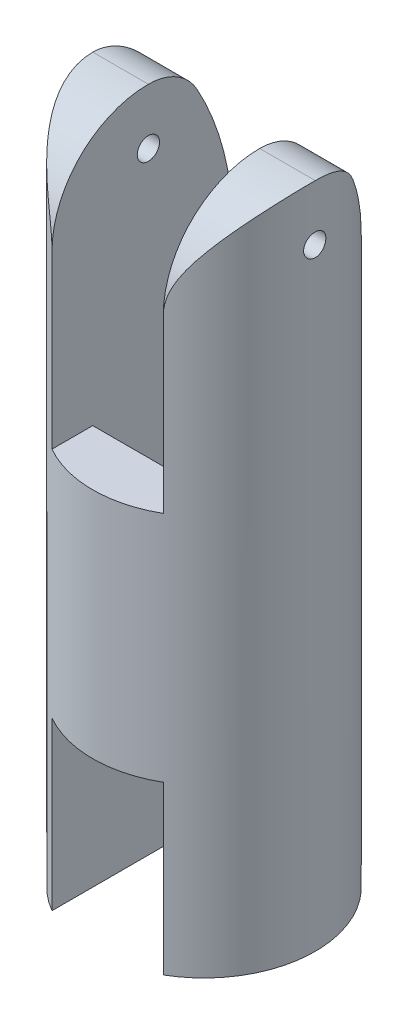
SolidWorks part; units mm, degrees
ref_plane "Front Plane" through (0, 0, 0) normal (0, 0, 1) x (1, 0, 0)
ref_plane "Top Plane" through (0, 0, 0) normal (0, 1, 0) x (1, 0, 0)
ref_plane "Right Plane" through (0, 0, 0) normal (1, 0, 0) x (0, 0, -1)
sketch "Sketch1" plane through (0, 0, 0) normal (0, 1, 0) x (1, 0, 0)
  circle A0 centre (0, 0) radius 5
  point P3 (-596.1263, -63.7666)
  dimension "D1" = 10
extrude "Boss-Extrude1" add sketch "Sketch1" along normal blind 7.5 and the other way blind 7.5
sketch "Sketch3" plane through (0, 7.5, 0) normal (0, 1, 0) x (1, 0, 0)
  line L0 (-2.5, 4.3301) -> (-2.5, -4.3301)
  line L1 (0, -55) -> (0, 55) construction
  line L2 (2.5, 4.3301) -> (2.5, -4.3301)
  circle A0 centre (0, 0) radius 5 construction
  arc A1 (-2.5, 4.3301) -> (-2.5, -4.3301) centre (0, 0) ccw
  arc A2 (2.5, 4.3301) -> (2.5, -4.3301) centre (0, 0) cw
  dimension "D1" = 2.5
extrude "Boss-Extrude3" add sketch "Sketch3" along normal blind 7.5
sketch "Sketch4" plane through (0, -7.5, 0) normal (0, -1, 0) x (1, 0, 0)
  line L0 (-2.5, 4.3301) -> (-2.5, -4.3301)
  line L1 (0, -5.5) -> (0, 5.5) construction
  line L2 (2.5, 4.3301) -> (2.5, -4.3301)
  arc A0 (-2.5, 4.3301) -> (-2.5, -4.3301) centre (0, 0) ccw
  arc A1 (2.5, 4.3301) -> (2.5, -4.3301) centre (0, 0) cw
  dimension "D2" = 5
  dimension "D1" = 2.5
extrude "Boss-Extrude4" add sketch "Sketch4" along normal blind 7.5
sketch "Sketch5" plane through (0, -7.5, 0) normal (0, -1, 0) x (1, 0, 0)
  line L0 (2.5, 4.3301) -> (2.5, -4.3301) construction
  line L1 (-2.5, -2.5) -> (2.5, -2.5)
  line L2 (-2.5, -2.5) -> (-2.5, 2.5)
  line L3 (-2.5, 2.5) -> (2.5, 2.5)
  line L4 (2.5, -2.5) -> (2.5, 2.5)
  line L5 (-2.5, -2.5) -> (2.5, 2.5) construction
  line L6 (-2.5, 2.5) -> (2.5, -2.5) construction
  point P0 (0, 0)
  dimension "D1" = 5
  dimension "D2" = 5
extrude "Cut-Extrude2" cut sketch "Sketch5" along normal through all and the other way through all
sketch "Sketch9" plane through (-2.5, 0, 0) normal (1, 0, 0) x (0, 0, -1)
  line L0 (4.3301, 15) -> (4.3301, 7.5) construction
  line L1 (-4.3301, 15) -> (4.3301, 15) construction
  point P0 (0, 12.5)
  point P5 (0, 0)
  dimension "D1" = 4.3301
  dimension "D2" = 2.5
sketch "Sketch10" plane through (-2.5, 0, 0) normal (1, 0, 0) x (0, 0, -1)
  line L1 (-4.3301, 15) -> (4.3301, 15) construction
  line L2 (0, 5.5) -> (0, -5.5) construction
  line L4 (-4.3301, 10.6699) -> (-4.3319, 15.1699)
  line L5 (-4.3319, 15.1699) -> (4.3284, 15.1699)
  line L6 (4.3284, 15.1699) -> (4.3301, 10.6699)
  arc A0 (4.3301, 10.6699) -> (-4.3301, 10.6699) centre (0, 10.6699) ccw
  point P0 (0, 10.6699)
  dimension "D4" = 4.3301
  dimension "D1" = 4.5
  dimension "D2" = 4.3301
  dimension "D3" = 8.6603
  dimension "D5" = 4.5
  dimension "D6" = 8.6603
  dimension "D7" = 4.5
extrude "Cut-Extrude4" cut sketch "Sketch10" against normal blind 7.5 and the other way through all
sketch "Sketch12" plane through (2.5, 0, 0) normal (-1, 0, 0) x (0, 0, 1)
  arc A0 (4.3301, 10.6699) -> (-4.3301, 10.6699) centre (0, 10.6699) ccw construction
  circle A1 centre (0, 12.5) radius 0.5
  point P0 (0, 12.5)
  point P4 (0, 15)
  dimension "D2" = 1
  dimension "D3" = 1.8301
  dimension "D1" = 2.5
hole_wizard "#97 (0.03937008) Diameter Hole1" positions "3DSketch1" profile "Sketch14" hole size "#97" standard "ANSI Inch" end condition through all
sketch3d "3DSketch1"
  point P0 (2.5, 12.5, 0)
sketch "Sketch14" plane through (2.5, 12.5, 0) normal (0, 1, 0) x (0, 0, 1)
  line L0 (0, 0) -> (0, 2.5)
  line L1 (0, 2.5) -> (0.5, 2.5)
  line L2 (0.5, 2.5) -> (0.5, 0)
  line L5 (0.5, 0) -> (0, 0)
  line L11 (0, -6.35) -> (0, 107.95) construction
  dimension "Thru Hole Dia." = 1
  dimension "Thru Hole Depth" = 2.5
hole_wizard "#97 (0.03937008) Diameter Hole2" positions "3DSketch2" profile "Sketch15" hole size "#97" standard "ANSI Inch"
sketch3d "3DSketch2"
  point P0 (2.5, 12.5, 0)
sketch "Sketch15" plane through (2.5, 12.5, 0) normal (0, 1, 0) x (0, 0, -1)
  line L0 (0, 0) -> (0, 10.3004)
  line L1 (0, 10.3004) -> (0.5, 10)
  line L2 (0.5, 10) -> (0.5, 0)
  line L5 (0.5, 0) -> (0, 0)
  line L10 (0, 10.3004) -> (-0.5, 10) construction
  line L11 (0, -6.35) -> (0, 107.95) construction
  dimension "Hole Dia." = 1
  dimension "Hole Depth" = 10
  dimension "Drill Angle" = 118
sketch "Sketch16" plane through (-2.5, 0, 0) normal (1, 0, 0) x (0, 0, -1)
  line L0 (5.4501, 3.3099) -> (7.392, 3.3099)
  line L1 (7.392, 3.3099) -> (7.392, 15)
  line L2 (7.392, 15) -> (0, 15)
  arc A0 (0, 15) -> (2.1896, 13.7065) centre (0, 12.5) cw
  arc A1 (4.3301, 10.6699) -> (-4.3301, 10.6699) centre (0, 10.6699) ccw construction
  arc A2 (2.1896, 13.7065) -> (3.7957, 7.4638) centre (-9.1396, 7.4638) cw
  arc A3 (3.7957, 7.4638) -> (5.4501, 3.3099) centre (9.8377, 7.4638) ccw
extrude "Cut-Extrude5" cut sketch "Sketch16" against normal blind 7.5 and the other way blind 7.5
sketch "Sketch17" plane through (0, 0, 0) normal (0, 0, 1) x (1, 0, 0)
  line L0 (2.5, 7.5638) -> (-2.5, 7.5638)
  line L1 (-2.5, 7.5638) -> (-2.5, 2.9638)
  line L2 (-2.5, 2.9638) -> (2.5, 2.9638)
  line L3 (2.5, 2.9638) -> (2.5, 7.5638)
  line L4 (3.2546, 7.4638) -> (-3.2546, 7.4638) construction
  dimension "D1" = 2.5
  dimension "D2" = 5
  dimension "D3" = 4.6
  dimension "D4" = 0.1
extrude "Cut-Extrude8" cut sketch "Sketch17" against normal blind 7.5 and the other way blind 7.5
